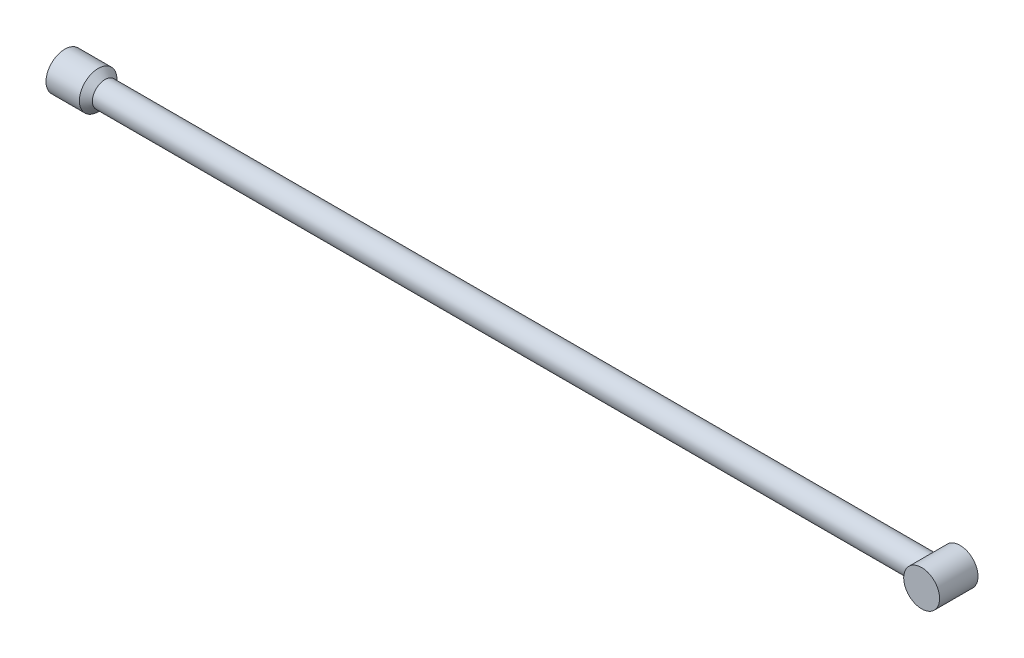
SolidWorks part; units mm, degrees
ref_plane "Front Plane" through (0, 0, 0) normal (0, 0, 1) x (1, 0, 0)
ref_plane "Top Plane" through (0, 0, 0) normal (0, 1, 0) x (1, 0, 0)
ref_plane "Right Plane" through (0, 0, 0) normal (1, 0, 0) x (0, 0, -1)
sketch "Sketch2" plane through (0, 0, 0) normal (1, 0, 0) x (0, 0, -1)
  circle A0 centre (0, 0) radius 75
  circle A1 centre (0, 0) radius 37.5
  dimension "D1" = 150
  dimension "D2" = 75
extrude "Boss-Extrude1" add sketch "Sketch2" along normal blind 5000
sketch "Sketch3" plane through (0, 0, 0) normal (-1, 0, 0) x (0, 0, 1)
  circle A0 centre (0, 0) radius 112.5
  circle A1 centre (0, 0) radius 92.5
  dimension "D1" = 225
  dimension "D2" = 185
extrude "Boss-Extrude2" add sketch "Sketch3" along normal blind 200
sketch "Sketch4" plane through (0, 0, 0) normal (0, 0, 1) x (1, 0, 0)
  circle A0 centre (5050.1346, 0) radius 107.5
  circle A1 centre (5050.1346, 0) radius 92.5
  point P2 (5050.1346, 0)
  dimension "D1" = 215
  dimension "D2" = 185
extrude "Boss-Extrude9" add sketch "Sketch4" along normal through all and the other way through all separate body
sketch "Sketch5" plane through (0, 0, 112.5) normal (0, 0, 1) x (1, 0, 0)
  circle A0 centre (5050.1346, 0) radius 75
extrude "Cut-Extrude1" cut sketch "Sketch5" against normal blind 175
sketch "Sketch6" plane through (0, 0, 0) normal (-1, 0, 0) x (0, 0, 1)
  circle A0 centre (0, 0) radius 37.5
extrude "Cut-Extrude2" cut sketch "Sketch6" against normal blind 5024
sketch "Sketch7" plane through (0, 0, 0) normal (0, 0, 1) x (1, 0, 0)
  line L0 (0, 112.5) -> (0, 75)
  line L1 (0, 75) -> (40.4361, 75)
  line L2 (5000, 75) -> (0, 75) construction
  line L3 (40.4361, 75) -> (0, 112.5)
  line L4 (-224.7945, 0) -> (133.1421, 0) construction
revolve "Revolve1" add sketch "Sketch7" angle 360 about L4
sketch "Sketch9" plane through (0, 0, 112.5) normal (0, 0, 1) x (1, 0, 0)
  circle A0 centre (5050.1346, 0) radius 107.5
  dimension "D1" = 215
extrude "Boss-Extrude10" add sketch "Sketch9" along normal blind 5 and the other way blind 5
sketch "Sketch10" plane through (0, 0, -112.5) normal (0, 0, -1) x (-1, 0, 0)
  circle A0 centre (-5050.1346, 0) radius 91.9114
  point P2 (-5050.1346, 0)
  point P4 (-5050.1346, 0)
extrude "Cut-Extrude3" cut sketch "Sketch10" against normal blind 202
